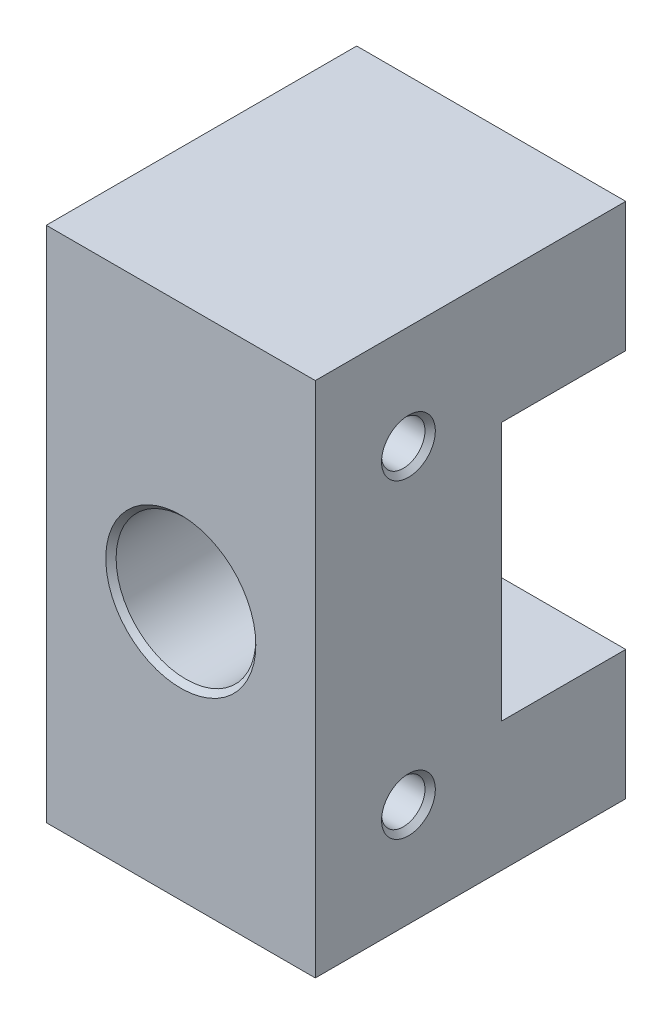
SolidWorks part; units mm, degrees
material "6061 Alloy"
ref_plane "Front Plane" through (0, 0, 0) normal (0, 0, 1) x (1, 0, 0)
ref_plane "Top Plane" through (0, 0, 0) normal (0, 1, 0) x (1, 0, 0)
ref_plane "Right Plane" through (0, 0, 0) normal (1, 0, 0) x (0, 0, -1)
sketch "Sketch1" plane through (0, 0, 0) normal (0, 0, 1) x (1, 0, 0)
  line L1 (-13, 25) -> (13, 25)
  line L2 (-13, 25) -> (-13, -25)
  line L3 (-13, -25) -> (13, -25)
  line L4 (13, 25) -> (13, -25)
  line L5 (-13, 25) -> (13, -25) construction
  line L6 (-13, -25) -> (13, 25) construction
  point P0 (0, 0)
  dimension "D1" = 50
  dimension "D2" = 26
extrude "Boss-Extrude1" add sketch "Sketch1" along normal blind 30
sketch "Sketch2" plane through (0, 0, 0) normal (0, 0, 1) x (1, 0, 0)
  line L0 (-13, 25) -> (-13, -25) construction
  line L1 (13, 12.5) -> (-13, 12.5)
  line L2 (13, 12.5) -> (13, -12.5)
  line L3 (13, -12.5) -> (-13, -12.5)
  line L4 (-13, 12.5) -> (-13, -12.5)
  line L5 (13, 12.5) -> (-13, -12.5) construction
  line L6 (13, -12.5) -> (-13, 12.5) construction
  point P0 (0, 0)
  dimension "D1" = 25
extrude "Cut-Extrude1" cut sketch "Sketch2" along normal blind 12
hole_wizard "M12 Clearance Hole1" positions "Sketch7" profile "Sketch8" hole size "M12" standard "ANSI Metric" end condition up to next
sketch "Sketch7" plane through (0, 0, 12) normal (0, 0, -1) x (-1, 0, 0)
  point P0 (0, 0)
sketch "Sketch8" plane through (0, 0, 12) normal (1, 0, 0) x (0, 1, 0)
  line L0 (0, 0) -> (0, 18)
  line L1 (0, 18) -> (6.75, 18)
  line L2 (6.75, 18) -> (6.75, 0)
  line L5 (6.75, 0) -> (0, 0)
  line L11 (0, -6.35) -> (0, 107.95) construction
  dimension "Thru Hole Dia." = 13.5
  dimension "Thru Hole Depth" = 18
hole_wizard "M5x0.8 Tapped Hole1" positions "Sketch10" profile "Sketch11" tap size "M5x0.8" standard "ANSI Metric"
sketch "Sketch10" plane through (13, 0, 0) normal (1, 0, 0) x (0, 0, -1)
  line L0 (-21, 15) -> (-21, -15) construction
  line L2 (-30, 0) -> (-12, 0) construction
  line L3 (-30, -25) -> (-30, 25) construction
  line L4 (-12, -12.5) -> (-12, 12.5) construction
  point P0 (-21, 15)
  point P2 (-21, -15)
  point P16 (-21, 0)
  dimension "D1" = 30
sketch "Sketch11" plane through (13, 15, 21) normal (0, 1, 0) x (0, 0, -1)
  line L0 (0, 0) -> (0, 12)
  line L1 (0, 12) -> (2.1, 10.7382)
  line L2 (2.1, 10.7382) -> (2.1, 0)
  line L5 (2.1, 0) -> (0, 0)
  line L10 (0, 12) -> (-2.1, 10.7382) construction
  line L11 (0, -6.35) -> (0, 107.95) construction
  dimension "Tap Drill Dia." = 4.2
  dimension "Tap Drill Depth" = 12
  dimension "Drill Angle" = 118
cosmetic thread "Hole Thread5"
cosmetic thread "Hole Thread6"
mirror "Mirror1" about plane through (0, 0, 0) normal (1, 0, 0) of "M5x0.8 Tapped Hole1"
cosmetic thread "Hole Thread7" parameters "D1"=10, "D2"=5
cosmetic thread "Hole Thread8" parameters "D1"=10, "D2"=5
chamfer "Chamfer1 0.5 mm" distance 0.5 angle 45 6 edges at (6.75, 0, 30) (-6.75, 0, 12) (13, -15, 18.9) (13, 15, 18.9) (-13, -15, 23.1) (-13, 15, 23.1)
